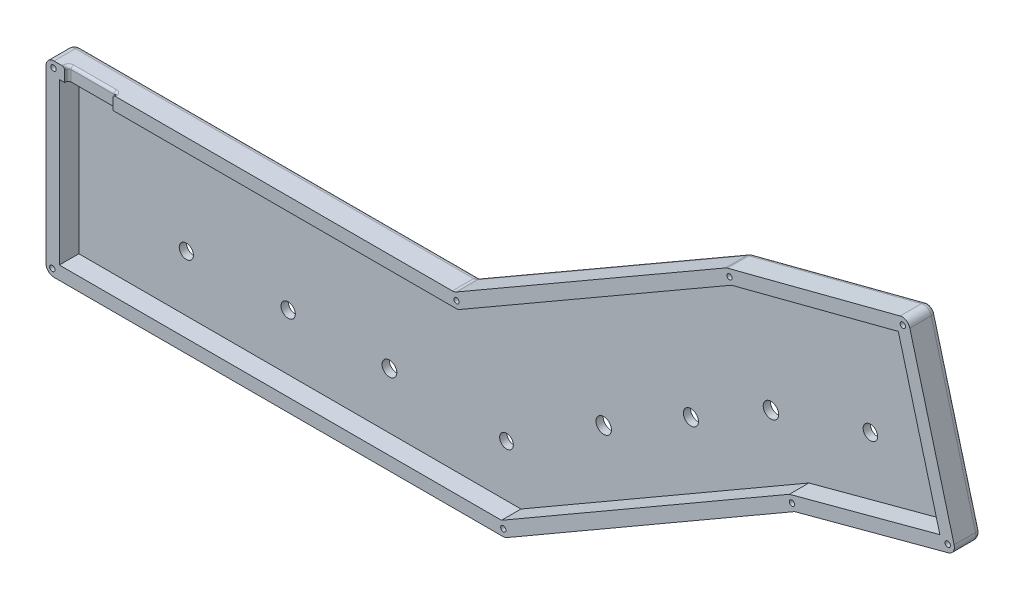
SolidWorks part; units mm, degrees
ref_plane "Plan de face" through (0, 0, 0) normal (0, 0, 1) x (1, 0, 0)
ref_plane "Plan de dessus" through (0, 0, 0) normal (0, 1, 0) x (1, 0, 0)
ref_plane "Plan de droite" through (0, 0, 0) normal (1, 0, 0) x (0, 0, -1)
sketch "Model" plane through (0, 0, 0) normal (0, 0, 1) x (1, 0, 0)
  line L0 (152.8114, 25.9717) -> (138.2826, 80.2215) construction
  line L1 (98.1506, 11.3316) -> (152.8114, 25.9717) construction
  line L2 (-9.3986, -50.8585) -> (98.1506, 11.3316) construction
  line L3 (-172.3739, -50.8585) -> (-9.3986, -50.8585) construction
  line L4 (-24.5886, 5.3017) -> (-172.3739, 5.2915) construction
  line L5 (138.2826, 80.2215) -> (78.0109, 64.5416) construction
  line L6 (-151.6088, 5.3124) -> (-151.6088, 5.2929)
  line L7 (-24.5886, 5.3017) -> (78.0109, 64.5416) construction
  line L8 (-172.3739, 5.2915) -> (-172.3739, -50.6876) construction
  line L9 (-172.3739, -50.6876) -> (-172.3739, -50.8585) construction
  line L10 (-25.1245, 7.3016) -> (-174.3739, 7.2914)
  line L11 (-174.3739, 7.2914) -> (-174.3739, -50.6876)
  line L12 (-174.3739, -50.6876) -> (-174.3739, -52.8585)
  line L13 (-174.3739, -52.8585) -> (-8.862, -52.8585)
  line L14 (-8.862, -52.8585) -> (98.9231, 9.4681)
  line L15 (98.9231, 9.4681) -> (155.2607, 24.5572)
  line L16 (155.2607, 24.5572) -> (139.7008, 82.657)
  line L17 (139.7008, 82.657) -> (77.2454, 66.409)
  line L18 (-25.1245, 7.3016) -> (77.2454, 66.409)
  line L19 (-26.4645, 12.3015) -> (-179.3739, 12.291)
  line L20 (-179.3739, 12.291) -> (-179.3739, -50.6876)
  line L21 (-179.3739, -50.6876) -> (-179.3739, -57.8585)
  line L22 (-179.3739, -57.8585) -> (-7.5204, -57.8585)
  line L23 (-7.5204, -57.8585) -> (100.8545, 4.8091)
  line L24 (100.8545, 4.8091) -> (161.3839, 21.021)
  line L25 (161.3839, 21.021) -> (143.2464, 88.7459)
  line L26 (143.2464, 88.7459) -> (75.3314, 71.0775)
  line L27 (-26.4645, 12.3015) -> (75.3314, 71.0775)
  circle A0 centre (80.6856, 58.4893) radius 1
  circle A1 centre (92.8776, 28.0855) radius 1
  circle A2 centre (-29.7028, -2.6485) radius 1
  circle A3 centre (-10.6528, -46.4381) radius 1
  circle A4 centre (-114.2594, -13.4181) radius 1
  circle A5 centre (-114.0308, -32.4935) radius 1
  dimension "D1" = 2
  dimension "D2" = 5
extrude "Boss.-Extru.1" add sketch "Model" along normal blind 10 contours L27 L19 L20 L21 L22 L23 L24 L25 L26 L10 L18 L17 L16 L15 L14 L13 L12 L11 region at (26.2883, 38.477, 0)
fillet "Congé1" radius 3 8 edges at (-26.4645, 12.3015, 5) (75.3314, 71.0775, 5) (143.2464, 88.7459, 5) (161.3839, 21.021, 5) (100.8545, 4.8091, 5) (-7.5204, -57.8585, 5) (-179.3739, -57.8585, 5) (-179.3739, 12.291, 5)
sketch "Esquisse1" plane through (0, 0, 0) normal (0, 0, 1) x (1, 0, 0)
  line L0 (-25.1245, 7.3016) -> (-174.3739, 7.2914) construction
  line L1 (-25.1245, 7.3016) -> (77.2454, 66.409) construction
  line L2 (139.7008, 82.657) -> (77.2454, 66.409) construction
  line L3 (155.2607, 24.5572) -> (139.7008, 82.657) construction
  line L4 (98.9231, 9.4681) -> (155.2607, 24.5572) construction
  line L5 (-8.862, -52.8585) -> (98.9231, 9.4681) construction
  line L6 (-174.3739, -52.8585) -> (-8.862, -52.8585) construction
  line L7 (-174.3739, -50.6876) -> (-174.3739, -52.8585) construction
  line L8 (-174.3739, 7.2914) -> (-174.3739, -50.6876) construction
  line L9 (-25.1245, 7.3016) -> (-174.3739, 7.2914)
  line L10 (-25.1245, 7.3016) -> (77.2454, 66.409)
  line L11 (139.7008, 82.657) -> (77.2454, 66.409)
  line L12 (155.2607, 24.5572) -> (139.7008, 82.657)
  line L13 (98.9231, 9.4681) -> (155.2607, 24.5572)
  line L14 (-8.862, -52.8585) -> (98.9231, 9.4681)
  line L15 (-174.3739, -52.8585) -> (-8.862, -52.8585)
  line L16 (-174.3739, -50.6876) -> (-174.3739, -52.8585)
  line L17 (-174.3739, 7.2914) -> (-174.3739, -50.6876)
extrude "Boss.-Extru.2" add sketch "Esquisse1" along normal blind 2.7
sketch "Esquisse3" plane through (0, 0, 0) normal (0, 0, 1) x (1, 0, 0)
  circle A0 centre (158.2016, 22.9581) radius 1
  circle A1 centre (141.3885, 85.5343) radius 1
  circle A2 centre (76.5002, 68.7766) radius 1
  circle A3 centre (99.8904, 7.0714) radius 1
  circle A4 centre (-8.1724, -55.2759) radius 1
  circle A5 centre (-25.6914, 9.9201) radius 1
  circle A6 centre (-176.5621, 9.9201) radius 1
  circle A7 centre (-177.0296, -55.2759) radius 1
sketch "Esquisse2" plane through (0, 0, 0) normal (0, 0, -1) x (-1, 0, 0)
  circle A0 centre (-80.6856, 58.4893) radius 1 construction
  circle A1 centre (-92.8776, 28.0855) radius 1 construction
  circle A2 centre (29.7028, -2.6485) radius 1 construction
  circle A3 centre (10.6528, -46.4381) radius 1 construction
  circle A4 centre (114.2594, -13.4181) radius 1 construction
  circle A5 centre (114.0308, -32.4935) radius 1 construction
  circle A6 centre (-80.6856, 58.4893) radius 1
  circle A7 centre (-92.8776, 28.0855) radius 1
  circle A8 centre (29.7028, -2.6485) radius 1
  circle A9 centre (10.6528, -46.4381) radius 1
  circle A10 centre (114.2594, -13.4181) radius 1
  circle A11 centre (114.0308, -32.4935) radius 1
  circle A12 centre (-80.6856, 58.4893) radius 2
  circle A13 centre (-92.8776, 28.0855) radius 2
  circle A14 centre (29.7028, -2.6485) radius 2
  circle A15 centre (10.6528, -46.4381) radius 2
  circle A16 centre (114.2594, -13.4181) radius 2
  circle A17 centre (114.0308, -32.4935) radius 2
  dimension "D1" = 1
fillet "Congé2" radius 2 16 edges at (100.8645, 4.785, 0) (46.844, -26.4224, 0) (-7.5479, -57.756, 0) (-92.3496, -57.8585, 0) (-178.4952, -56.9798, 0) (-179.3739, -22.7836, 0) (-178.4953, 11.4125, 0) (-101.8212, 12.2964, 0) (-26.4919, 12.4038, 0) (24.6056, 41.7889, 0) (75.3418, 71.0522, 0) (108.0441, 79.5878, 0) (142.6286, 87.6851, 0) (152.3124, 54.8937, 0) (160.3079, 21.6424, 0) (129.8616, 12.5782, 0)
extrude "Enlèv. mat.-Extru.1" cut sketch "Esquisse3" along normal blind 20
sketch "Esquisse4" plane through (0, 0, 0) normal (0, 0, -1) x (-1, 0, 0)
  circle A0 centre (177.0296, -55.2759) radius 2
  circle A1 centre (176.5621, 9.9201) radius 2
  circle A2 centre (25.6914, 9.9201) radius 2
  circle A3 centre (-76.5002, 68.7766) radius 2
  circle A4 centre (-141.3885, 85.5343) radius 2
  circle A5 centre (-158.2016, 22.9581) radius 2
  circle A6 centre (-99.8904, 7.0714) radius 2
  circle A7 centre (8.1724, -55.2759) radius 2
extrude "Enlèv. mat.-Extru.2" cut sketch "Esquisse4" against normal blind 2
sketch "Esquisse5" plane through (-0.0008, 12.3034, 0) normal (-0.0001, 1, 0) x (1, 0.0001, 0)
  line L0 (-27.2675, -2) -> (-176.3732, -2) construction
  line L1 (-171.3732, -8.6) -> (-155.3732, -8.6)
  line L2 (-172.3732, -9.6) -> (-172.3732, -18.1)
  line L3 (-172.3732, -18.1) -> (-154.3732, -18.1)
  line L4 (-154.3732, -9.6) -> (-154.3732, -18.1)
  line L5 (-176.3732, -2) -> (-176.3732, -10) construction
  arc A0 (-155.3732, -8.6) -> (-154.3732, -9.6) centre (-155.3732, -9.6) cw
  arc A1 (-171.3732, -8.6) -> (-172.3732, -9.6) centre (-171.3732, -9.6) ccw
  point P10 (-154.3732, -8.6)
  dimension "D4" = 1
  dimension "D1" = 6.6
  dimension "D2" = 4
  dimension "D3" = 9.5
  dimension "D5" = 18
extrude "Enlèv. mat.-Extru.3" cut sketch "Esquisse5" against normal blind 10
fillet "Congé3" radius 1 5 edges at (-154.3741, 12.2928, 9.8) (-154.667, 12.2927, 8.8929) (-172.3741, 12.2915, 9.8) (-172.0812, 12.2915, 8.8929) (-163.3741, 12.2921, 8.6)
sketch "Esquisse7" plane through (0, 0, 2.7) normal (0, 0, 1) x (1, 0, 0)
  circle A0 centre (-134.1394, -31.928) radius 2.6575
  circle A1 centre (-96.0262, -31.928) radius 2.6813
  circle A2 centre (-58.1085, -31.928) radius 2.7625
  circle A3 centre (-14.2866, -33.5542) radius 2.56
  circle A4 centre (22.1119, -10.2814) radius 2.8929
  circle A5 centre (54.7478, 8.6934) radius 2.8222
  circle A6 centre (84.7109, 25.9763) radius 2.8889
  circle A7 centre (121.9376, 37.3583) radius 2.6958
extrude "Enlèv. mat.-Extru.4" cut sketch "Esquisse7" against normal blind 10
